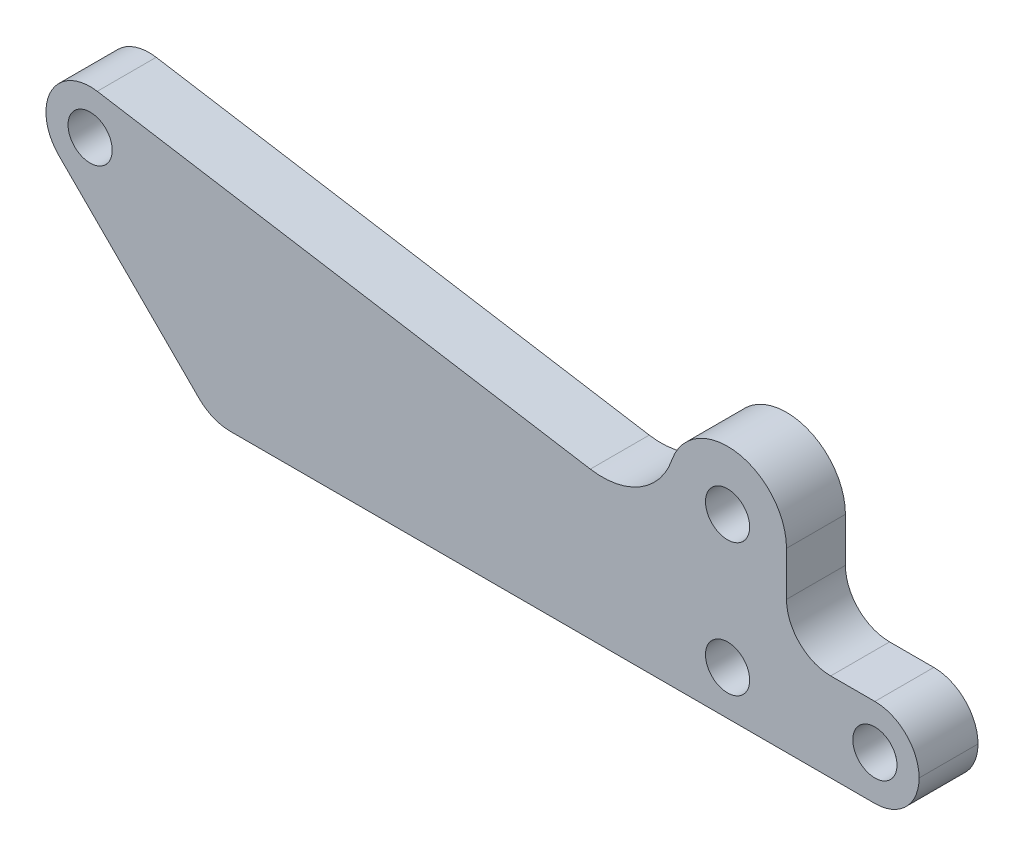
SolidWorks part; units mm, degrees
ref_plane "Front Plane" through (0, 0, 0) normal (0, 0, 1) x (1, 0, 0)
ref_plane "Top Plane" through (0, 0, 0) normal (0, 1, 0) x (1, 0, 0)
ref_plane "Right Plane" through (0, 0, 0) normal (1, 0, 0) x (0, 0, -1)
sketch "Sketch1" plane through (0, 0, 0) normal (0, 0, 1) x (1, 0, 0)
  line L0 (0, 0) -> (48, 0)
  line L1 (0, 0) -> (-10.3923, 10.3923)
  line L2 (-7.7868, 15.4743) -> (25.6848, 10)
  line L3 (39, 6) -> (39, 12)
  line L4 (39, 6) -> (48, 6)
  line L5 (48, 6) -> (48, 0)
  arc A0 (25.6848, 10) -> (31.2186, 13.3042) centre (26.4918, 14.9344) ccw
  arc A1 (31.2186, 13.3042) -> (39, 12) centre (35, 12) cw
  circle A2 centre (35, 12) radius 1.5
  circle A3 centre (-8.271, 12.5136) radius 1.5
  circle A4 centre (35, 3) radius 1.5
  circle A5 centre (45, 3) radius 1.5
  arc A6 (-10.3923, 10.3923) -> (-7.7868, 15.4743) centre (-8.271, 12.5136) cw
  point P4 (-8.7365, 10.1993)
  point P9 (0, 0)
  point P21 (0, 0)
  point P22 (0, 0)
  point P23 (23.9406, 13.5288)
  point P24 (0, 0)
  dimension "D1" = 3
  dimension "D6" = 3
  dimension "D8" = 5
  dimension "D13" = 4
  dimension "D2" = 3
  dimension "D3" = 135
  dimension "D4" = 15
  dimension "D5" = 35
  dimension "D7" = 10
  dimension "D9" = 12
  dimension "D10" = 3
  dimension "D11" = 10
  dimension "D12" = 6
extrude "Boss-Extrude1" add sketch "Sketch1" along normal blind 4
fillet "Fillet1" radius 3 4 edges at (48, 0, 2) (48, 6, 2) (39, 6, 2) (0, 0, 2)
